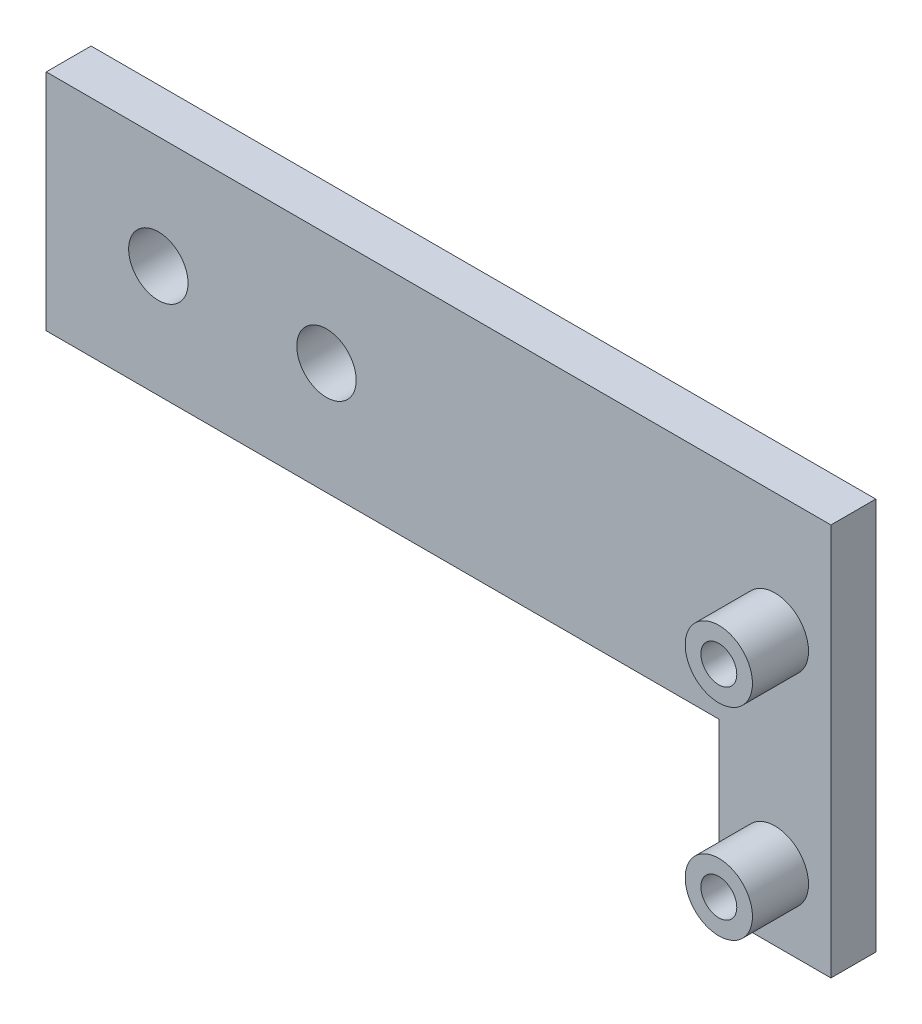
SolidWorks part; units mm, degrees
ref_plane "Front Plane" through (0, 0, 0) normal (0, 0, 1) x (1, 0, 0)
ref_plane "Top Plane" through (0, 0, 0) normal (0, 1, 0) x (1, 0, 0)
ref_plane "Right Plane" through (0, 0, 0) normal (1, 0, 0) x (0, 0, -1)
sketch "Sketch1" plane through (0, 0, 0) normal (0, 0, 1) x (1, 0, 0)
  line L0 (0, 0) -> (0, 35.2)
  line L1 (0, 0) -> (-40.2961, 0)
  line L2 (-40.2961, 0) -> (-40.2961, 35.2)
  line L3 (0, 35.2) -> (-40.2961, 35.2)
  line L4 (-20, 8.45) -> (-20, 0)
  line L5 (-20, 8.45) -> (-40.2961, 8.45)
  line L6 (-20, 26.45) -> (-40.2961, 26.45)
  line L7 (-20, 26.45) -> (-20, 35.2)
  line L8 (-20, 8.45) -> (-20, -2.8)
  line L9 (-20, -2.8) -> (-20, 37.2)
  line L11 (-25, 37.2) -> (-15, 37.2)
  line L12 (-25, 37.2) -> (-25, -2.8)
  line L13 (-25, -2.8) -> (-15, -2.8)
  line L14 (-15, 37.2) -> (-15, -2.8)
  line L15 (-40, 37.2) -> (0, 37.2)
  line L16 (-40, 37.2) -> (-40, 17.2)
  line L17 (-40, 17.2) -> (0, 17.2)
  line L18 (0, 37.2) -> (0, 17.2)
  circle A0 centre (-20, 26.45) radius 1.6
  circle A1 centre (-20, 8.45) radius 1.6
  dimension "D8" = 3.2
  dimension "D1" = 20.2961
  dimension "D2" = 8.45
  dimension "D3" = 20.2961
  dimension "D4" = 8.75
  dimension "D5" = 18
  dimension "D6" = 40.2961
  dimension "D7" = 0
  dimension "D9" = 11.25
  dimension "D10" = 40
  dimension "D11" = 40
  dimension "D12" = 10
  dimension "D13" = 5
  dimension "D14" = 20
  dimension "D15" = 0
  dimension "D16" = 20
  dimension "D17" = 40
extrude "Boss-Extrude1" add sketch "Sketch1" along normal blind 4 contours A1 L9 L1 L14 L17 | A1 L9 L17 L12 L5 | A1 L5 L12 L1 L9 | L12 L13 L8 L1 | L14 L1 L8 L13 | A0 L9 L17 L14 L3 | A0 L6 L12 L17 L9 | A0 L9 L3 L12 L6 | L14 L11 L9 L3 | L11 L12 L3 L9 | L18 L15 L14 L3 | L15 L16 L3 L12 | L3 L16 L6 L12 | L16 L17 L12 L6 | L14 L17 L0 L3 region at (-7.5, 26.2, 0) region at (-17.5, -1.4, 0) region at (-17.4107, 8.6074, 0) region at (-7.5, 36.2, 0) region at (-17.4148, 26.1883, 0) region at (-22.5, -1.4, 0) region at (-22.591, 4.0478, 0) region at (-17.5, 36.2, 0) region at (-22.5828, 21.6457, 0) region at (-22.5877, 13.003, 0) region at (-22.5877, 31.003, 0) region at (-22.5, 36.2, 0) region at (-32.5, 21.825, 0) region at (-32.5, 30.825, 0) region at (-32.5, 36.2, 0)
sketch "Sketch2" plane through (0, 0, 4) normal (0, 0, 1) x (1, 0, 0)
  line L0 (-5, 27.2) -> (-35, 27.2)
  line L1 (0, 17.2) -> (0, 37.2) construction
  line L2 (-40, 37.2) -> (0, 37.2) construction
  circle A0 centre (-35, 27.2) radius 2.5
  circle A1 centre (-5, 27.2) radius 2.5
  dimension "D3" = 5
  dimension "D4" = 5
  dimension "D1" = 30
  dimension "D2" = 5
  dimension "D5" = 10
extrude "Cut-Extrude1" cut sketch "Sketch2" against normal blind 13 contours A0 | A1 region at (-37.4293, 27.2, 4) region at (-5, 29.6293, 4)
sketch "Sketch3" plane through (0, 0, 4) normal (0, 0, 1) x (1, 0, 0)
  circle A0 centre (-20, 26.45) radius 3
  circle A1 centre (-20, 8.45) radius 3
  circle A2 centre (-20, 26.45) radius 1.6
  circle A3 centre (-20, 8.45) radius 1.6
  dimension "D1" = 6
  dimension "D2" = 6
  dimension "D3" = 3.2
  dimension "D4" = 3.2
extrude "Boss-Extrude2" add sketch "Sketch3" along normal blind 5
sketch "Sketch4" plane through (0, 0, 0) normal (0, 0, -1) x (-1, 0, 0)
  circle A0 centre (20, 26.45) radius 2.5
  circle A1 centre (20, 8.45) radius 2.5
  dimension "D1" = 5
  dimension "D2" = 5
extrude "Cut-Extrude3" cut sketch "Sketch4" against normal blind 3
sketch "Sketch5" plane through (0, 0, 4) normal (0, 0, 1) x (1, 0, 0)
  line L1 (0, 37.2) -> (45, 37.2)
  line L2 (0, 37.2) -> (0, 17.2)
  line L3 (0, 17.2) -> (45, 17.2)
  line L4 (45, 37.2) -> (45, 17.2)
  circle A0 centre (20, 27.2) radius 2.65
  circle A1 centre (35, 27.2) radius 2.65
  dimension "D3" = 5.3
  dimension "D4" = 5.3
  dimension "D5" = 10
  dimension "D6" = 15
  dimension "D8" = 10
  dimension "D1" = 45
  dimension "D2" = 20
  dimension "D7" = 10
extrude "Boss-Extrude3" add sketch "Sketch5" against normal up to surface (4 mm away) up to face at (-22.5, 26.45, 0)
sketch "Sketch6" plane through (0, 0, 4) normal (0, 0, 1) x (1, 0, 0)
  line L1 (-40, 37.2) -> (-25, 37.2)
  line L2 (-40, 37.2) -> (-40, 17.2)
  line L3 (-40, 17.2) -> (-25, 17.2)
  line L4 (-25, 37.2) -> (-25, 17.2)
sketch "Sketch7" plane through (0, 0, 4) normal (0, 0, 1) x (1, 0, 0)
  circle A0 centre (-5, 27.2) radius 3
  dimension "D1" = 6
extrude "Boss-Extrude4" add sketch "Sketch7" against normal up to surface (4 mm away) up to face at (-22.5, 26.45, 0)
ref_plane "Plane1" through (-20, 0, 0) normal (1, 0, 0) x (0, 0, -1)
mirror "Mirror1" about plane through (-20, 0, 0) normal (1, 0, 0) of "Boss-Extrude4"
mirror "Mirror2" about plane through (-20, 0, 0) normal (1, 0, 0) of "Boss-Extrude3"
sketch "Sketch8" plane through (0, 0, 4) normal (0, 0, 1) x (1, 0, 0)
  line L0 (-85, 37.2) -> (45, 37.2) construction
  line L1 (45, 17.2) -> (-15, 17.2)
  line L2 (45, 17.2) -> (45, 37.2)
  line L3 (45, 37.2) -> (-15, 37.2)
  line L4 (-15, 17.2) -> (-15, 37.2)
  line L5 (-15, 17.2) -> (-15, -2.8) construction
  dimension "D1" = 0
extrude "Cut-Extrude5" cut sketch "Sketch8" against normal blind 10
sketch "Sketch9" plane through (0, 0, 4) normal (0, 0, 1) x (1, 0, 0)
  line L0 (-15, 37.2) -> (-15, -2.8) construction
  line L1 (-25, -2.8) -> (-15, -2.8)
  line L2 (-25, -2.8) -> (-25, 2.2)
  line L3 (-25, 2.2) -> (-15, 2.2)
  line L4 (-15, -2.8) -> (-15, 2.2)
  dimension "D1" = 5
extrude "Cut-Extrude6" cut sketch "Sketch9" against normal blind 10
